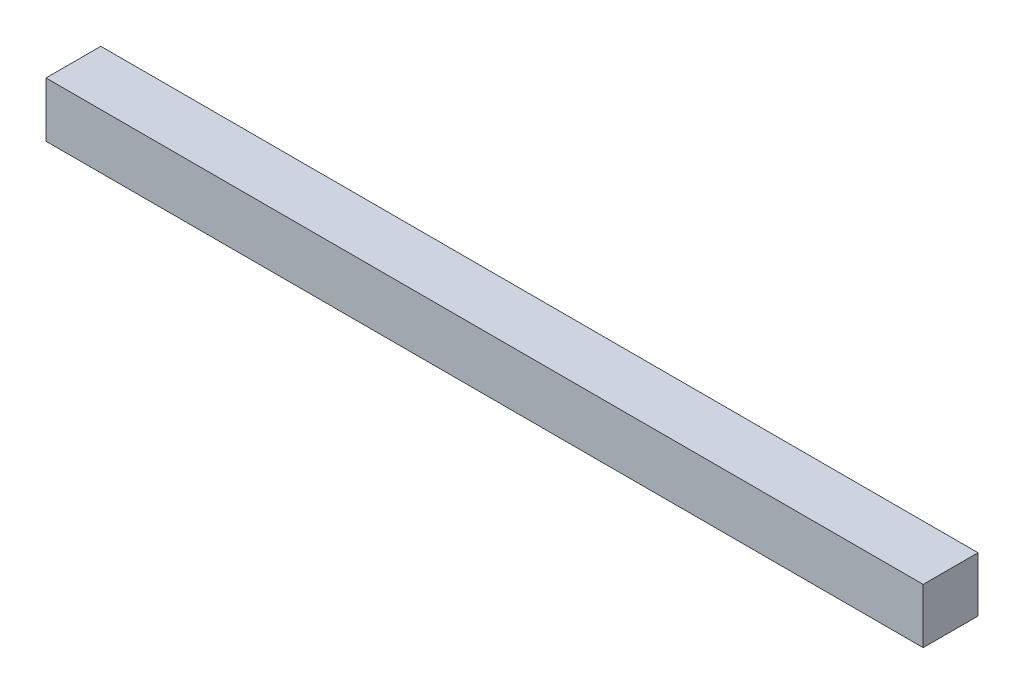
SolidWorks part; units mm, degrees
material "Alloy Steel"
ref_plane "Front Plane" through (0, 0, 0) normal (0, 0, 1) x (1, 0, 0)
ref_plane "Top Plane" through (0, 0, 0) normal (0, 1, 0) x (1, 0, 0)
ref_plane "Right Plane" through (0, 0, 0) normal (1, 0, 0) x (0, 0, -1)
sketch "Sketch2" plane through (0, 0, 0) normal (1, 0, 0) x (0, 0, -1)
  line L1 (3.175, -3.175) -> (-3.175, -3.175)
  line L2 (3.175, -3.175) -> (3.175, 3.175)
  line L3 (3.175, 3.175) -> (-3.175, 3.175)
  line L4 (-3.175, -3.175) -> (-3.175, 3.175)
  line L5 (3.175, -3.175) -> (-3.175, 3.175) construction
  line L6 (3.175, 3.175) -> (-3.175, -3.175) construction
  point P0 (0, 0)
  dimension "D1" = 6.35
  dimension "D2" = 6.35
extrude "Boss-Extrude1" add sketch "Sketch2" along normal mid plane 101.6
